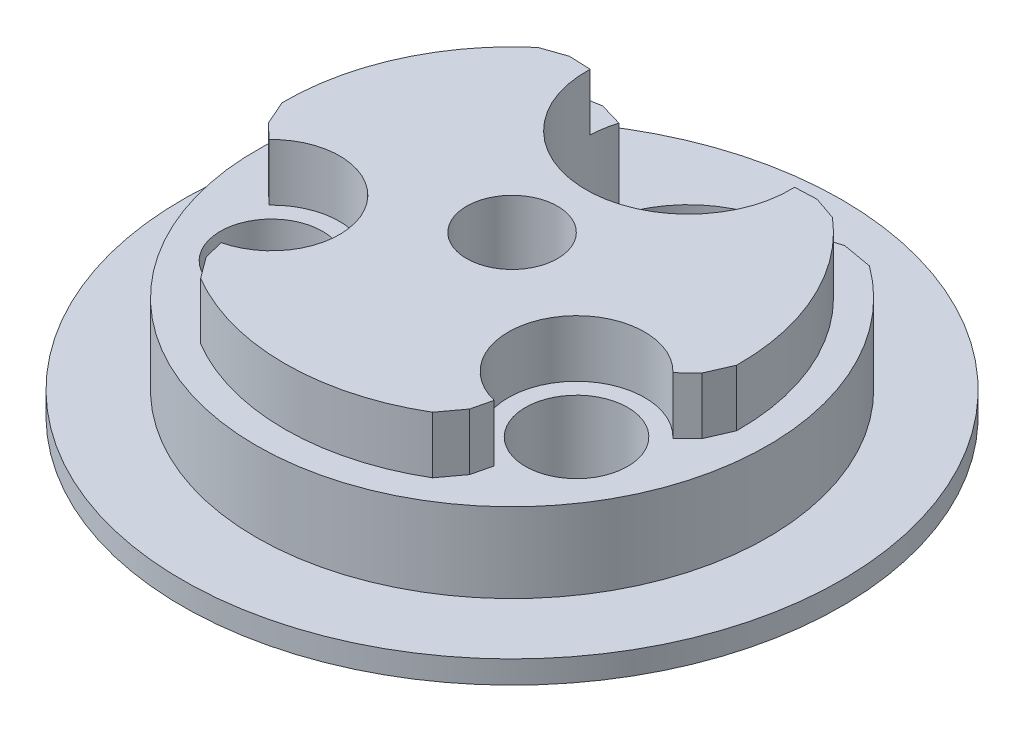
SolidWorks part; units mm, degrees
ref_plane "Front Plane" through (0, 0, 0) normal (0, 0, 1) x (1, 0, 0)
ref_plane "Top Plane" through (0, 0, 0) normal (0, 1, 0) x (1, 0, 0)
ref_plane "Right Plane" through (0, 0, 0) normal (1, 0, 0) x (0, 0, -1)
sketch "Sketch1" plane through (0, 0, 0) normal (0, 1, 0) x (1, 0, 0)
  circle A0 centre (0, 0) radius 22.5
  circle A1 centre (0, 15.5) radius 9
  circle A2 centre (13.4234, -7.75) radius 9
  circle A3 centre (-13.4234, -7.75) radius 9
  dimension "D1" = 45
  dimension "D3" = 18
  dimension "D2" = 15.5
  dimension "D4" = 3
extrude "Boss-Extrude1" add sketch "Sketch1" along normal blind 7 contours A3 A0 A2 A1
sketch "Sketch2" plane through (0, 7, 0) normal (0, 1, 0) x (1, 0, 0)
  line L6 (-19.9404, -1.5429) -> (-13.4234, -7.75)
  line L7 (-13.4234, -7.75) -> (-11.3064, -16.4975)
  line L8 (11.3064, -16.4975) -> (13.4234, -7.75)
  line L9 (13.4234, -7.75) -> (19.9404, -1.5429)
  arc A1 (-12.3649, -12.1237) -> (-16.6819, -4.6464) centre (-13.4234, -7.75) ccw
  arc A5 (16.6819, -4.6464) -> (12.3649, -12.1237) centre (13.4234, -7.75) ccw
  arc A6 (-15.2232, -16.5682) -> (-21.9601, -4.8995) centre (-13.4234, -7.75) ccw
  arc A7 (-15.2232, -16.5682) -> (15.2232, -16.5682) centre (0, 0) ccw
  arc A8 (21.9601, -4.8995) -> (15.2232, -16.5682) centre (13.4234, -7.75) ccw
  arc A9 (21.9601, -4.8995) -> (6.7369, 21.4677) centre (0, 0) ccw
  arc A10 (-6.7369, 21.4677) -> (6.7369, 21.4677) centre (0, 15.5) ccw
  arc A11 (-6.7369, 21.4677) -> (-21.9601, -4.8995) centre (0, 0) ccw
  arc A12 (-11.3064, -16.4975) -> (-19.9404, -1.5429) centre (-13.4234, -7.75) ccw
  arc A14 (19.9404, -1.5429) -> (11.3064, -16.4975) centre (13.4234, -7.75) ccw
  arc A16 (-8.634, 18.0403) -> (8.634, 18.0403) centre (0, 15.5) ccw
  arc A19 (-8.634, 18.0403) -> (-19.9404, -1.5429) centre (0, 0) ccw
  arc A24 (19.9404, -1.5429) -> (8.634, 18.0403) centre (0, 0) ccw
  arc A25 (3.3685, 18.4839) -> (0, 20) centre (0, 15.5) ccw [skipped]
  arc A27 (-11.3064, -16.4975) -> (11.3064, -16.4975) centre (0, 0) ccw
  arc A28 (-12.012, -13.5816) -> (-17.7681, -3.6119) centre (-13.4234, -7.75) ccw
  arc A32 (17.7681, -3.6119) -> (12.012, -13.5816) centre (13.4234, -7.75) ccw
  dimension "D3" = 9
  dimension "D1" = 0
  dimension "D4" = 3
extrude "Boss-Extrude3" add sketch "Sketch2" along normal blind 5 and the other way blind 7
sketch "Sketch3" plane through (0, 0, 0) normal (0, -1, 0) x (1, 0, 0)
  line L4 (19.9404, 1.5429) -> (16.6819, 4.6464)
  line L5 (12.3649, 12.1237) -> (11.3064, 16.4975)
  line L6 (-11.3064, 16.4975) -> (-12.3649, 12.1237)
  line L7 (-16.6819, 4.6464) -> (-19.9404, 1.5429)
  line L8 (19.9404, 1.5429) -> (16.6819, 4.6464)
  line L9 (12.3649, 12.1237) -> (11.3064, 16.4975)
  line L10 (-11.3064, 16.4975) -> (-12.3649, 12.1237)
  line L11 (-16.6819, 4.6464) -> (-19.9404, 1.5429)
  circle A0 centre (0, -15.5) radius 9
  arc A1 (-21.9601, 4.8995) -> (-15.2232, 16.5682) centre (-13.4234, 7.75) ccw
  arc A2 (15.2232, 16.5682) -> (21.9601, 4.8995) centre (13.4234, 7.75) ccw
  circle A3 centre (-13.4234, 7.75) radius 4.5
  circle A4 centre (13.4234, 7.75) radius 4.5
  circle A5 centre (0, 0) radius 22.5
  arc A10 (19.9404, 1.5429) -> (21.9601, 4.8995) centre (13.4234, 7.75) ccw
  arc A11 (12.3649, 12.1237) -> (16.6819, 4.6464) centre (13.4234, 7.75) ccw
  arc A12 (15.2232, 16.5682) -> (11.3064, 16.4975) centre (13.4234, 7.75) ccw
  arc A13 (15.2232, 16.5682) -> (-15.2232, 16.5682) centre (0, 0) ccw
  arc A14 (-11.3064, 16.4975) -> (-15.2232, 16.5682) centre (-13.4234, 7.75) ccw
  arc A15 (-16.6819, 4.6464) -> (-12.3649, 12.1237) centre (-13.4234, 7.75) ccw
  arc A16 (-21.9601, 4.8995) -> (-19.9404, 1.5429) centre (-13.4234, 7.75) ccw
  arc A17 (-21.9601, 4.8995) -> (-6.7369, -21.4677) centre (0, 0) ccw
  arc A18 (6.7369, -21.4677) -> (-6.7369, -21.4677) centre (0, -15.5) ccw
  arc A19 (6.7369, -21.4677) -> (21.9601, 4.8995) centre (0, 0) ccw
  arc A20 (19.9404, 1.5429) -> (21.9601, 4.8995) centre (13.4234, 7.75) ccw
  arc A21 (12.3649, 12.1237) -> (16.6819, 4.6464) centre (13.4234, 7.75) ccw
  arc A22 (15.2232, 16.5682) -> (11.3064, 16.4975) centre (13.4234, 7.75) ccw
  arc A23 (15.2232, 16.5682) -> (-15.2232, 16.5682) centre (0, 0) ccw
  arc A24 (-11.3064, 16.4975) -> (-15.2232, 16.5682) centre (-13.4234, 7.75) ccw
  arc A25 (-16.6819, 4.6464) -> (-12.3649, 12.1237) centre (-13.4234, 7.75) ccw
  arc A26 (-21.9601, 4.8995) -> (-19.9404, 1.5429) centre (-13.4234, 7.75) ccw
  arc A27 (-21.9601, 4.8995) -> (-6.7369, -21.4677) centre (0, 0) ccw
  arc A28 (6.7369, -21.4677) -> (-6.7369, -21.4677) centre (0, -15.5) ccw
  arc A29 (6.7369, -21.4677) -> (21.9601, 4.8995) centre (0, 0) ccw
  arc M17 (21.9601, 4.8995) -> (19.9404, 1.5429) centre (13.4234, 7.75) cw
  line M18 (19.9404, 1.5429) -> (16.6819, 4.6464)
  arc M19 (16.6819, 4.6464) -> (12.3649, 12.1237) centre (13.4234, 7.75) cw
  line M20 (12.3649, 12.1237) -> (11.3064, 16.4975)
  arc M21 (11.3064, 16.4975) -> (15.2232, 16.5682) centre (13.4234, 7.75) cw
  arc M23 (-15.2232, 16.5682) -> (-11.3064, 16.4975) centre (-13.4234, 7.75) cw
  line M24 (-11.3064, 16.4975) -> (-12.3649, 12.1237)
  arc M25 (-12.3649, 12.1237) -> (-16.6819, 4.6464) centre (-13.4234, 7.75) cw
  line M26 (-16.6819, 4.6464) -> (-19.9404, 1.5429)
  arc M27 (-19.9404, 1.5429) -> (-21.9601, 4.8995) centre (-13.4234, 7.75) cw
  dimension "D1" = 0
  dimension "D2" = 3
extrude "Boss-Extrude5" add sketch "Sketch3" against normal blind 7 contours A5 A3 M23 M27 M26 M24 | A1 M26 M24 M25 | A5 A4 M17 M21 M20 M18 | A2 M20 M18 M19
sketch "Sketch4" plane through (0, 12, 0) normal (0, 1, 0) x (1, 0, 0)
  line L4 (16.6819, -4.6464) -> (19.9404, -1.5429)
  line L5 (-19.9404, -1.5429) -> (-16.6819, -4.6464)
  line L6 (-12.3649, -12.1237) -> (-11.3064, -16.4975)
  line L7 (11.3064, -16.4975) -> (12.3649, -12.1237)
  line L8 (16.6819, -4.6464) -> (19.9404, -1.5429)
  line L9 (-19.9404, -1.5429) -> (-16.6819, -4.6464)
  line L10 (-12.3649, -12.1237) -> (-11.3064, -16.4975)
  line L11 (11.3064, -16.4975) -> (12.3649, -12.1237)
  circle A0 centre (-13.4234, -7.75) radius 6
  circle A1 centre (13.4234, -7.75) radius 6
  arc A6 (19.9404, -1.5429) -> (8.634, 18.0403) centre (0, 0) ccw
  arc A7 (-8.634, 18.0403) -> (8.634, 18.0403) centre (0, 15.5) ccw
  arc A8 (-8.634, 18.0403) -> (-19.9404, -1.5429) centre (0, 0) ccw
  arc A9 (-12.3649, -12.1237) -> (-16.6819, -4.6464) centre (-13.4234, -7.75) ccw
  arc A10 (-11.3064, -16.4975) -> (11.3064, -16.4975) centre (0, 0) ccw
  arc A11 (16.6819, -4.6464) -> (12.3649, -12.1237) centre (13.4234, -7.75) ccw
  arc A12 (19.9404, -1.5429) -> (8.634, 18.0403) centre (0, 0) ccw
  arc A13 (-8.634, 18.0403) -> (8.634, 18.0403) centre (0, 15.5) ccw
  arc A14 (-8.634, 18.0403) -> (-19.9404, -1.5429) centre (0, 0) ccw
  arc A15 (-12.3649, -12.1237) -> (-16.6819, -4.6464) centre (-13.4234, -7.75) ccw
  arc A16 (-11.3064, -16.4975) -> (11.3064, -16.4975) centre (0, 0) ccw
  arc A17 (16.6819, -4.6464) -> (12.3649, -12.1237) centre (13.4234, -7.75) ccw
  line M12 (16.6819, -4.6464) -> (19.9404, -1.5429)
  arc M17 (-16.6819, -4.6464) -> (-12.3649, -12.1237) centre (-13.4234, -7.75) cw
  line M18 (-12.3649, -12.1237) -> (-11.3064, -16.4975)
  arc M21 (12.3649, -12.1237) -> (16.6819, -4.6464) centre (13.4234, -7.75) cw
  dimension "D2" = 12
  dimension "D1" = 0
extrude "Cut-Extrude1" cut sketch "Sketch4" against normal blind 5 contours A0 L9 M18 M17 | A1 L11 M12 M21
sketch "Sketch5" plane through (0, 12, 0) normal (0, 1, 0) x (1, 0, 0)
  circle A0 centre (0, 0) radius 4
  dimension "D1" = 8
extrude "Cut-Extrude2" cut sketch "Sketch5" against normal through all
sketch "Sketch6" plane through (0, 0, 0) normal (0, -1, 0) x (1, 0, 0)
  circle A0 centre (0, 0) radius 29
  circle A1 centre (0, -15.5) radius 9
  arc A2 (6.7369, -21.4677) -> (-6.7369, -21.4677) centre (0, -15.5) ccw
  arc A3 (6.7369, -21.4677) -> (-6.7369, -21.4677) centre (0, 0) ccw
  arc A4 (6.7369, -21.4677) -> (-6.7369, -21.4677) centre (0, -15.5) ccw
  arc A5 (6.7369, -21.4677) -> (-6.7369, -21.4677) centre (0, 0) ccw
  circle M4 centre (0, 0) radius 4
  arc M5 (-6.7369, -21.4677) -> (6.7369, -21.4677) centre (0, -15.5) cw
  arc M6 (6.7369, -21.4677) -> (-6.7369, -21.4677) centre (0, 0) ccw
  circle M7 centre (13.4234, 7.75) radius 4.5
  circle M8 centre (-13.4234, 7.75) radius 4.5
  dimension "D2" = 58
  dimension "D1" = 0
extrude "Boss-Extrude7" add sketch "Sketch6" along normal blind 2 contours A0 A1 M6 | M6 M5 M8 M7 M4
sketch "Sketch7" plane through (0, 12, 0) normal (0, 1, 0) x (1, 0, 0)
  line L0 (8.6358, 18.0344) -> (12.012, 19.0253)
  line L1 (-8.6358, 18.0344) -> (-12.012, 19.0253)
  line L2 (-12.012, 15.991) -> (-8.9925, 15.8675)
  line L3 (8.9925, 15.8675) -> (12.012, 15.991)
  line L4 (-12.012, -13.5816) -> (-11.3064, -16.4975)
  line L5 (11.3064, -16.4975) -> (12.012, -13.5816)
  line L6 (17.7681, -3.6119) -> (19.9404, -1.5429)
  line L7 (-19.9404, -1.5429) -> (-17.7681, -3.6119)
  line L8 (-12.012, -13.5816) -> (-11.3064, -16.4975)
  line L9 (11.3064, -16.4975) -> (12.012, -13.5816)
  line L10 (17.7681, -3.6119) -> (19.9404, -1.5429)
  line L11 (-19.9404, -1.5429) -> (-17.7681, -3.6119)
  line L12 (-11.3064, -16.4975) -> (-12.012, -13.5816)
  line L13 (-17.7681, -3.6119) -> (-19.9404, -1.5429)
  line L14 (19.9404, -1.5429) -> (17.7681, -3.6119)
  line L15 (12.012, -13.5816) -> (11.3064, -16.4975)
  line L16 (-11.3064, -16.4975) -> (-12.012, -13.5816)
  line L17 (-17.7681, -3.6119) -> (-19.9404, -1.5429)
  line L18 (19.9404, -1.5429) -> (17.7681, -3.6119)
  line L19 (12.012, -13.5816) -> (11.3064, -16.4975)
  arc A0 (12.012, 19.0253) -> (6.7369, 21.4677) centre (0, 0) ccw
  arc A1 (-6.7369, 21.4677) -> (6.7369, 21.4677) centre (0, 15.5) ccw
  arc A6 (-12.012, -13.5816) -> (-17.7681, -3.6119) centre (-13.4234, -7.75) ccw
  arc A7 (-11.3064, -16.4975) -> (11.3064, -16.4975) centre (0, 0) ccw
  arc A8 (17.7681, -3.6119) -> (12.012, -13.5816) centre (13.4234, -7.75) ccw
  arc A9 (19.9404, -1.5429) -> (8.634, 18.0403) centre (0, 0) ccw
  arc A10 (-8.634, 18.0403) -> (8.634, 18.0403) centre (0, 15.5) ccw
  arc A11 (-8.634, 18.0403) -> (-19.9404, -1.5429) centre (0, 0) ccw
  arc A12 (-12.012, -13.5816) -> (-17.7681, -3.6119) centre (-13.4234, -7.75) ccw
  arc A13 (-11.3064, -16.4975) -> (11.3064, -16.4975) centre (0, 0) ccw
  arc A14 (17.7681, -3.6119) -> (12.012, -13.5816) centre (13.4234, -7.75) ccw
  arc A15 (12.012, 15.991) -> (8.634, 18.0403) centre (0, 0) ccw
  arc A16 (-8.634, 18.0403) -> (8.634, 18.0403) centre (0, 15.5) ccw
  arc A17 (-8.634, 18.0403) -> (-12.012, 15.991) centre (0, 0) ccw
  arc A20 (-12.012, -13.5816) -> (-17.7681, -3.6119) centre (-13.4234, -7.75) ccw
  arc A21 (-8.634, 18.0403) -> (-19.9404, -1.5429) centre (0, 0) ccw
  arc A22 (-6.7369, 21.4677) -> (-8.634, 18.0403) centre (0, 15.5) ccw
  arc A23 (-6.7369, 21.4677) -> (6.7369, 21.4677) centre (0, 0) ccw
  arc A24 (8.634, 18.0403) -> (6.7369, 21.4677) centre (0, 15.5) ccw
  arc A25 (19.9404, -1.5429) -> (8.634, 18.0403) centre (0, 0) ccw
  arc A26 (17.7681, -3.6119) -> (12.012, -13.5816) centre (13.4234, -7.75) ccw
  arc A27 (-11.3064, -16.4975) -> (11.3064, -16.4975) centre (0, 0) ccw
  arc A28 (-12.012, -13.5816) -> (-17.7681, -3.6119) centre (-13.4234, -7.75) ccw
  arc A29 (-8.634, 18.0403) -> (-12.012, 15.991) centre (0, 0) ccw
  arc A30 (-6.7369, 21.4677) -> (-8.634, 18.0403) centre (0, 15.5) ccw
  arc A31 (-6.7369, 21.4677) -> (-12.012, 19.0253) centre (0, 0) ccw
  arc A32 (8.634, 18.0403) -> (6.7369, 21.4677) centre (0, 15.5) ccw
  arc A33 (12.012, 15.991) -> (8.634, 18.0403) centre (0, 0) ccw
  arc A34 (17.7681, -3.6119) -> (12.012, -13.5816) centre (13.4234, -7.75) ccw
  arc A35 (-11.3064, -16.4975) -> (11.3064, -16.4975) centre (0, 0) ccw
  arc M30 (19.9404, -1.5429) -> (8.634, 18.0403) centre (0, 0) ccw
  arc M31 (8.634, 18.0403) -> (-8.634, 18.0403) centre (0, 15.5) cw
  arc M32 (-8.634, 18.0403) -> (-19.9404, -1.5429) centre (0, 0) ccw
  dimension "D1" = 0
  dimension "D2" = 0
extrude "Cut-Extrude6" cut sketch "Sketch7" against normal up to surface (12 mm away) contours A1 L0 A0 M30 | L0 M31 M30 | L3 L0 M31 M30 | A1 A31 L1 M32 | L2 L1 M32 M31 | L1 M31 M32
sketch "Sketch8" plane through (0, 0, 0) normal (0, 1, 0) x (1, 0, 0)
  line L2 (-12.012, 15.991) -> (-8.9925, 15.8675)
  line L3 (8.9925, 15.8675) -> (12.012, 15.991)
  arc A2 (12.012, 15.991) -> (8.634, 18.0403) centre (0, 0) ccw
  arc A3 (-8.634, 18.0403) -> (-8.9925, 15.8675) centre (0, 15.5) ccw
  arc A4 (-8.634, 18.0403) -> (-12.012, 15.991) centre (0, 0) ccw
  arc A5 (8.9925, 15.8675) -> (-8.9925, 15.8675) centre (0, 15.5) ccw construction
  arc A6 (8.9925, 15.8675) -> (8.634, 18.0403) centre (0, 15.5) ccw
extrude "Boss-Extrude8" add sketch "Sketch8" along normal up to surface (7 mm away) up to face at (0, 7, -0.0359)
fillet "Fillet1" radius 3 8 edges at (19.9404, 9.5, 1.5429) (11.3064, 9.5, 16.4975) (-12.012, 3.5, -19.0253) (12.012, 3.5, -19.0253) (12.012, 9.5, -15.991) (-12.012, 9.5, -15.991) (-19.9404, 9.5, 1.5429) (-11.3064, 9.5, 16.4975)
